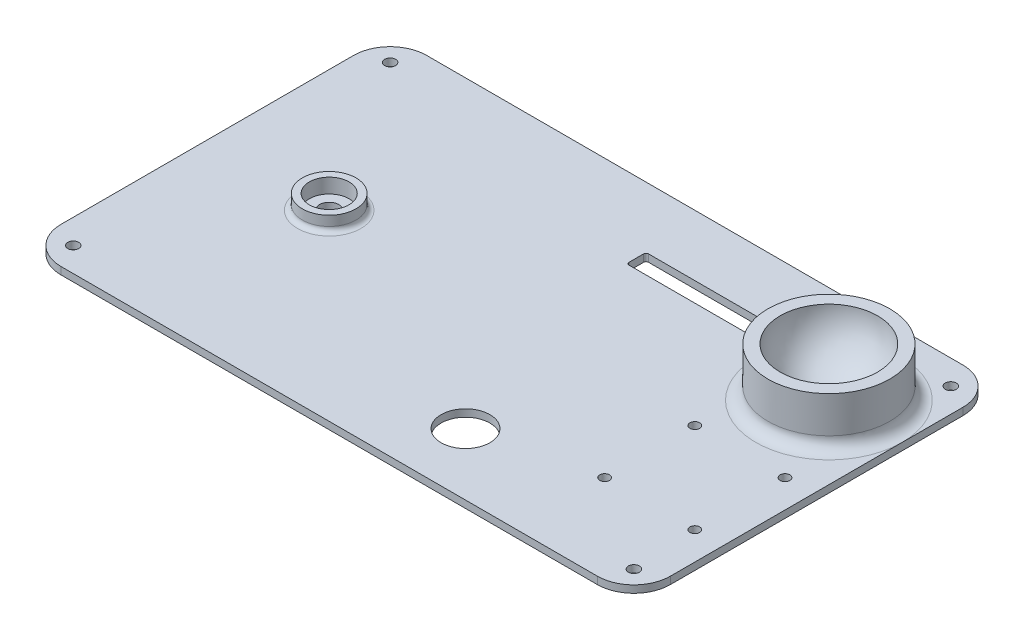
SolidWorks part; units mm, degrees
material "ABS"
ref_plane "Alzado" through (0, 0, 0) normal (0, 0, 1) x (1, 0, 0)
ref_plane "Planta" through (0, 0, 0) normal (0, 1, 0) x (1, 0, 0)
ref_plane "Vista lateral" through (0, 0, 0) normal (1, 0, 0) x (0, 0, -1)
sketch "Croquis1" plane through (0, 0, 0) normal (0, 1, 0) x (1, 0, 0)
  line L1 (-125, -75) -> (125, -75)
  line L2 (-125, -75) -> (-125, 75)
  line L3 (-125, 75) -> (125, 75)
  line L4 (125, -75) -> (125, 75)
  line L5 (-125, -75) -> (125, 75) construction
  line L6 (-125, 75) -> (125, -75) construction
  point P0 (0, 0)
  dimension "D1" = 250
  dimension "D2" = 150
extrude "Saliente-Extruir1" add sketch "Croquis1" along normal blind 3
fillet "Redondeo1" radius 15 4 edges at (-125, 1.5, -75) (125, 1.5, -75) (125, 1.5, 75) (-125, 1.5, 75)
sketch "Croquis2" plane through (0, 3, 0) normal (0, 1, 0) x (1, 0, 0)
  line L2 (0, 98.6503) -> (0, -114.3648) construction
  line L3 (-199.0405, 0) -> (132.2006, 0) construction
  line L4 (110, 75) -> (-110, 75) construction
  line L5 (-125, 60) -> (-125, -60) construction
  circle A0 centre (-115, 65) radius 2.25
  circle A1 centre (115, 65) radius 2.25
  circle A2 centre (115, -65) radius 2.25
  circle A3 centre (-115, -65) radius 2.25
  point P0 (-115, 65)
  point P11 (115, 65)
  point P13 (115, -65)
  point P15 (-115, -65)
  dimension "D1" = 0
  dimension "D3" = 10
  dimension "D4" = 10
  dimension "D5" = 4.5
  dimension "D2" = 0
extrude "Cortar-Extruir1" cut sketch "Croquis2" against normal up to next
sketch "Croquis3" plane through (0, 3, 0) normal (0, 1, 0) x (1, 0, 0)
  line L0 (-125, 60) -> (-125, -60) construction
  line L1 (-75, 0) -> (-15, 0)
  circle A0 centre (-75, 0) radius 4
  circle A1 centre (-15, 0) radius 7
  dimension "D1" = 8
  dimension "D2" = 50
  dimension "D4" = 14
  dimension "D3" = 60
extrude "Cortar-Extruir2" cut sketch "Croquis3" against normal blind 5 contours A0 region at (-78.8869, 3, 0)
sketch "Croquis4" plane through (0, 3, 0) normal (0, 1, 0) x (1, 0, 0)
  circle A0 centre (-75, 0) radius 8.15
  circle A1 centre (-75, 0) radius 11
  dimension "D1" = 16.3
  dimension "D2" = 22
extrude "Saliente-Extruir2" add sketch "Croquis4" along normal blind 6
fillet "Redondeo2" radius 2 1 edges at (-75, 3, -11)
sketch "Croquis5" plane through (0, 3, 0) normal (0, 1, 0) x (1, 0, 0)
  line L0 (125, -60) -> (125, 60) construction
  line L1 (-110, -75) -> (110, -75) construction
  circle A0 centre (95, 35) radius 20
  circle A1 centre (95, 35) radius 25
  dimension "D1" = 40
  dimension "D2" = 30
  dimension "D3" = 110
  dimension "D4" = 50
extrude "Saliente-Extruir3" add sketch "Croquis5" along normal blind 20
fillet "Redondeo3" radius 20 1 edges at (95, 3, -15)
fillet "Redondeo4" radius 5 1 edges at (95, 3, -60)
sketch "Croquis6" plane through (0, 3, 0) normal (0, 1, 0) x (1, 0, 0)
  line L0 (125, -60) -> (125, 35) construction
  line L1 (72.5, -42.5) -> (117.5, -42.5)
  line L2 (72.5, -42.5) -> (72.5, 2.5)
  line L3 (72.5, 2.5) -> (117.5, 2.5)
  line L4 (117.5, -42.5) -> (117.5, 2.5)
  line L5 (72.5, -42.5) -> (117.5, 2.5) construction
  line L6 (72.5, 2.5) -> (117.5, -42.5) construction
  circle A0 centre (95, -20) radius 20.5
  circle A1 centre (95, 35) radius 20 construction
  circle A2 centre (113.5, -1.5) radius 2
  circle A3 centre (113.5, -38.5) radius 2
  circle A4 centre (76.5, -38.5) radius 2
  circle A5 centre (76.5, -1.5) radius 2
  dimension "D1" = 41
  dimension "D2" = 55
  dimension "D5" = 30
  dimension "D6" = 4
  dimension "D7" = 4
  dimension "D8" = 4
  dimension "D9" = 4
  dimension "D10" = 4
  dimension "D11" = 4
  dimension "D12" = 4
  dimension "D13" = 4
  dimension "D14" = 4
  dimension "D16" = 4
  dimension "D17" = 4
  dimension "D3" = 45
  dimension "D4" = 45
  dimension "D15" = 4
sketch "Croquis11" plane through (0, 3, 0) normal (0, 1, 0) x (1, 0, 0)
  line L0 (110, 75) -> (-110, 75) construction
  line L1 (5, 50) -> (65, 50)
  line L2 (5, 50) -> (5, 42)
  line L3 (5, 42) -> (65, 42)
  line L4 (65, 50) -> (65, 42)
  line L5 (-141.9786, 0) -> (187.3412, 0) construction
  line L10 (125, -60) -> (125, 35) construction
  dimension "D1" = 8
  dimension "D2" = 60
  dimension "D3" = 25
  dimension "D4" = 60
extrude "Cortar-Extruir6" cut sketch "Croquis11" against normal blind 20
fillet "Redondeo7" radius 1 4 edges at (5, 1.5, -42) (5, 1.5, -50) (65, 1.5, -50) (65, 1.5, -42)
sketch "Croquis12" plane through (0, 3, 0) normal (0, 1, 0) x (1, 0, 0)
  circle A0 centre (30.5724, -49.6493) radius 10
  dimension "D1" = 20
extrude "Cortar-Extruir7" cut sketch "Croquis12" against normal blind 200
extrude "Cortar-Extruir8" cut sketch "Croquis6" against normal blind 10 contours A2 | A5 | A4 | A3
